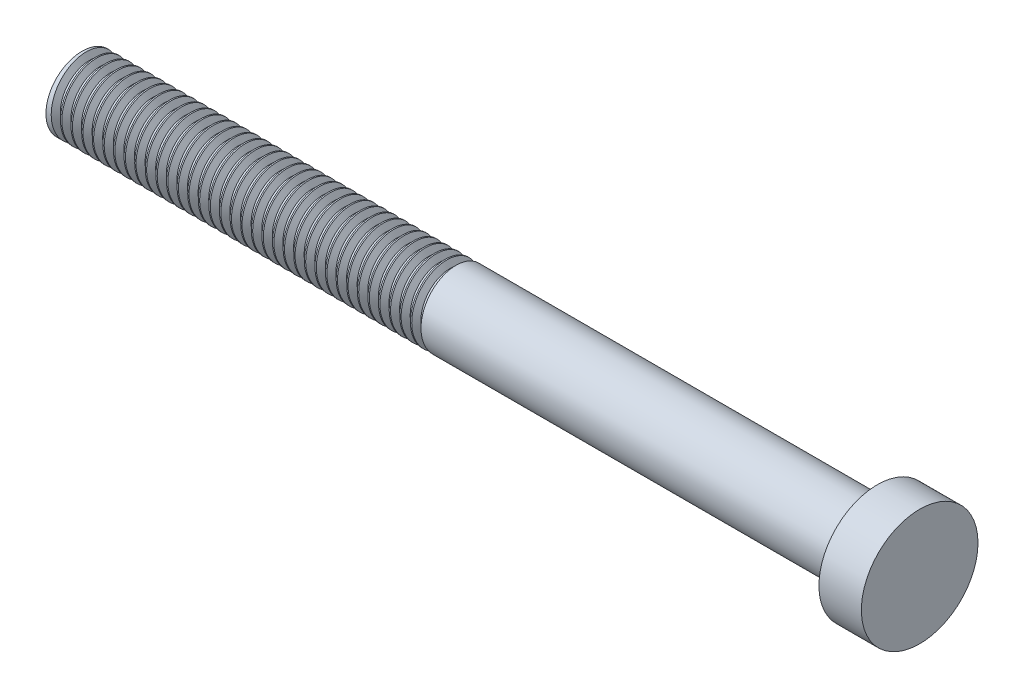
SolidWorks part; units mm, degrees
ref_plane "Plan de face" through (0, 0, 0) normal (0, 0, 1) x (1, 0, 0)
ref_plane "Plan de dessus" through (0, 0, 0) normal (0, 1, 0) x (1, 0, 0)
ref_plane "Plan de droite" through (0, 0, 0) normal (1, 0, 0) x (0, 0, -1)
sketch "Esquisse1" plane through (0, 0, 0) normal (1, 0, 0) x (0, 0, -1)
  circle A0 centre (0, 0) radius 5.5
  dimension "D1" = 11
extrude "Boss.-Extru.1" add sketch "Esquisse1" along normal blind 4
sketch "Esquisse2" plane through (0, 0, 0) normal (-1, 0, 0) x (0, 0, 1)
  circle A0 centre (0, 0) radius 3.4
  dimension "D1" = 6.8
extrude "Boss.-Extru.2" add sketch "Esquisse2" along normal blind 75
thread "Filetage1" pitch 1 method cut profile "Profil de filetage1" start angle 0, offset 0, length 35, pitch 1, diameter 6.8
ref_plane "Plan1" through (-75, 0, -3.4) normal (0, -1, 0) x (0, 0, -1)
sketch "Profil de filetage1" plane through (-75, 0, -3.4) normal (0, -1, 0) x (0, 0, -1)
  line L0 (0, 0) -> (0, 1) construction
  line L11 (0, 0) -> (0, 0.875)
  line L12 (0, 0.875) -> (-0.5413, 0.5625)
  line L13 (-0.5413, 0.5625) -> (-0.5413, 0.3125)
  line L15 (-0.5413, 0.3125) -> (0, 0)
  line L17 (-0.5413, 0.4375) -> (0, 0.4375) construction
  point P2 (0, 0)
  dimension "Pitch" = 1
  dimension "Profile_Angle" = 60
  dimension "Profile_Land" = 0.25
  dimension "Profile_Height" = 0.5413
